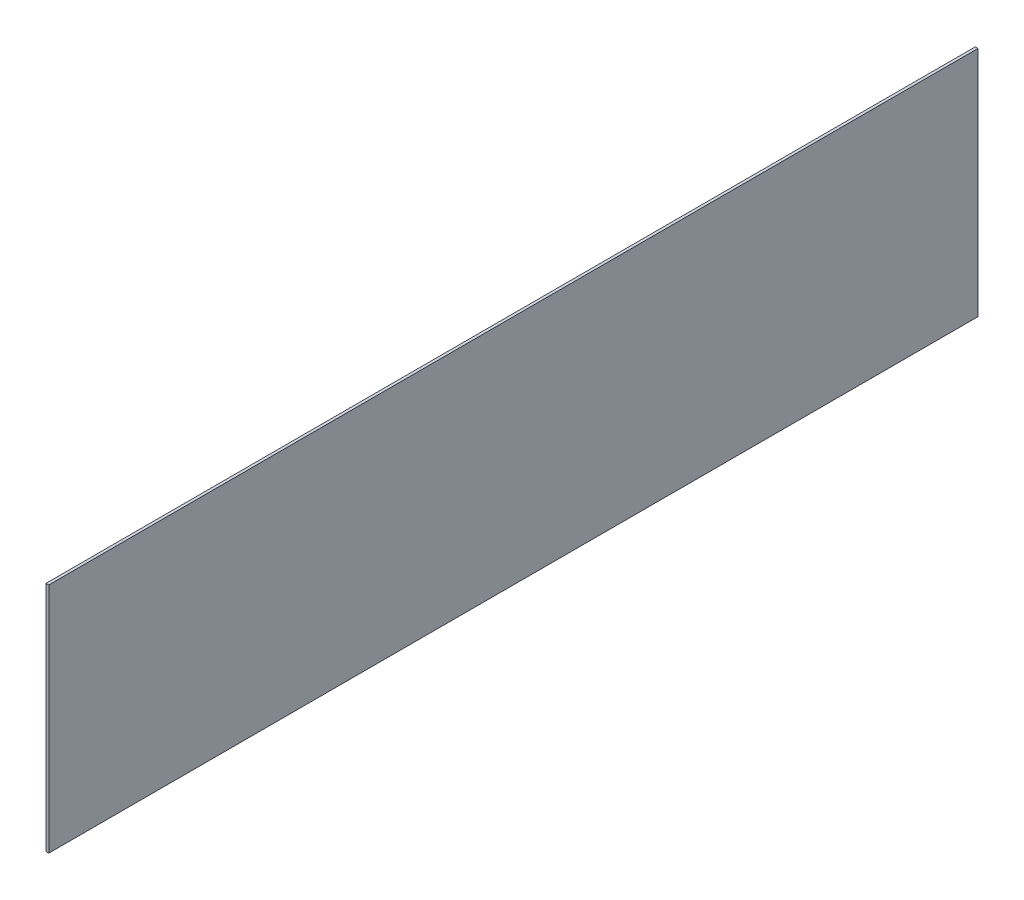
SolidWorks part; units mm, degrees
ref_plane "Front Plane" through (0, 0, 0) normal (0, 0, 1) x (1, 0, 0)
ref_plane "Top Plane" through (0, 0, 0) normal (0, 1, 0) x (1, 0, 0)
ref_plane "Right Plane" through (0, 0, 0) normal (1, 0, 0) x (0, 0, -1)
sketch "Sketch1" plane through (0, 0, 0) normal (1, 0, 0) x (0, 0, -1)
  line L1 (0, 0) -> (533.4, 0)
  line L2 (0, 0) -> (0, 133.35)
  line L3 (0, 133.35) -> (533.4, 133.35)
  line L4 (533.4, 0) -> (533.4, 133.35)
  dimension "D1" = 133.35
  dimension "D2" = 533.4
extrude "Boss-Extrude1" add sketch "Sketch1" along normal blind 1.5875
